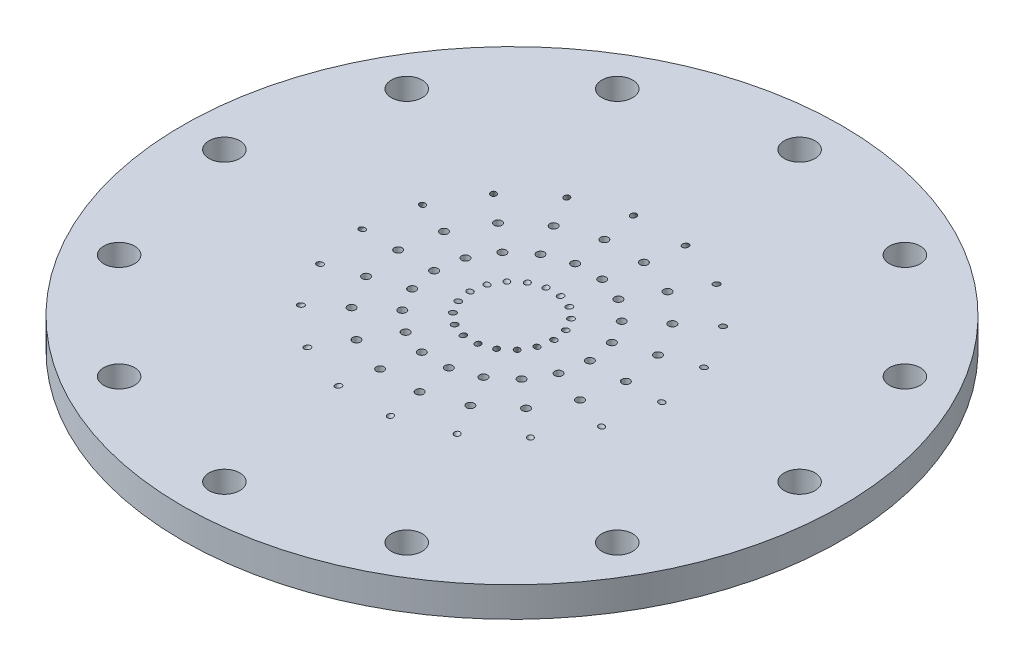
SolidWorks part; units mm, degrees
material "6061-T6 (SS)"
ref_plane "Front Plane" through (0, 0, 0) normal (0, 0, 1) x (1, 0, 0)
ref_plane "Top Plane" through (0, 0, 0) normal (0, 1, 0) x (1, 0, 0)
ref_plane "Right Plane" through (0, 0, 0) normal (1, 0, 0) x (0, 0, -1)
sketch "Sketch1" plane through (0, 0, 0) normal (0, 1, 0) x (1, 0, 0)
  circle A0 centre (0, 0) radius 69.85
  dimension "D1" = 139.7
extrude "Boss-Extrude1" add sketch "Sketch1" along normal blind 6.35 contours A0
sketch "Sketch2" plane through (0, 6.35, 0) normal (0, 1, 0) x (1, 0, 0)
  circle A0 centre (0, 0) radius 8.89
  circle A1 centre (0, 0) radius 16.51
  circle A2 centre (0, 0) radius 24.13
  circle A3 centre (0, 0) radius 31.75
  dimension "D1" = 17.78
  dimension "D2" = 33.02
  dimension "D3" = 48.26
  dimension "D4" = 63.5
sketch "Sketch3" plane through (0, 0, 0) normal (0, 0, 1) x (1, 0, 0)
  line L0 (8.89, 6.35) -> (0, -9.0479)
  line L1 (8.89, 6.35) -> (-8.89, 6.35) construction
  line L2 (16.51, 6.35) -> (-16.51, 6.35) construction
  line L3 (0, 0) -> (0, -9.0479) construction
  line L4 (0, -9.0479) -> (-8.5376, -4.1187) construction
  dimension "D1" = 30
ref_plane "Plane1" through (-3.9179, -6.7859, 0) normal (0.5, 0.866, 0) x (-0.866, 0.5, 0)
sketch "Sketch4" plane through (-3.9179, -6.7859, 0) normal (0.5, 0.866, 0) x (-0.866, 0.5, 0)
  line L0 (-4.524, 0) -> (5.3344, 0) construction
  circle A0 centre (-4.524, 0) radius 0.5906
  dimension "D1" = 1.1811
extrude "Cut-Extrude1" cut sketch "Sketch4" along normal through all
sketch "Sketch5" plane through (0, 0, 0) normal (0, 0, 1) x (1, 0, 0)
  line L0 (31.75, 6.35) -> (35.4162, 0)
  line L3 (31.75, 6.35) -> (-31.75, 6.35) construction
  line L4 (35.4162, 0) -> (0, 0) construction
  line L5 (31.75, 6.35) -> (52.6029, 18.3894) construction
  dimension "D1" = 60
ref_plane "Plane2" through (5.1879, -8.9857, 0) normal (0.5, -0.866, 0) x (0.866, 0.5, 0)
sketch "Sketch6" plane through (5.1879, -8.9857, 0) normal (0.5, -0.866, 0) x (0.866, 0.5, 0)
  circle A0 centre (30.6713, 0) radius 0.5906
  dimension "D1" = 1.1811
extrude "Cut-Extrude2" cut sketch "Sketch6" against normal through all both and the other way through all
sketch "Sketch7" plane through (0, 6.35, 0) normal (0, 1, 0) x (1, 0, 0)
  line L0 (0, 0) -> (31.75, 0) construction
  circle A0 centre (0, 0) radius 31.75 construction
  circle A1 centre (24.13, 0) radius 0.8255
  circle A2 centre (0, 0) radius 24.13 construction
  circle A3 centre (16.51, 0) radius 0.8255
  circle A7 centre (0, 0) radius 16.51 construction
  dimension "D1" = 1.651
extrude "LOx Holes" cut sketch "Sketch7" against normal through all both and the other way through all
pattern_circular "CirPattern1" count 18 over 360 about axis through (0, 6.35, 0) along (0, -1, 0) of "Cut-Extrude1", "Cut-Extrude2", "LOx Holes" reverse direction yes
sketch "Sketch8" plane through (0, 0, 0) normal (0, -1, 0) x (1, 0, 0)
  circle A0 centre (0, 0) radius 60.96 construction
  circle A1 centre (-60.96, 0) radius 3.2639
  dimension "D1" = 121.92
  dimension "D2" = 6.5278
extrude "Cut-Extrude4" cut sketch "Sketch8" against normal through all
pattern_circular "CirPattern2" count 12 over 360 about axis through (0, 6.35, 0) along (0, -1, 0) of "Cut-Extrude4"
